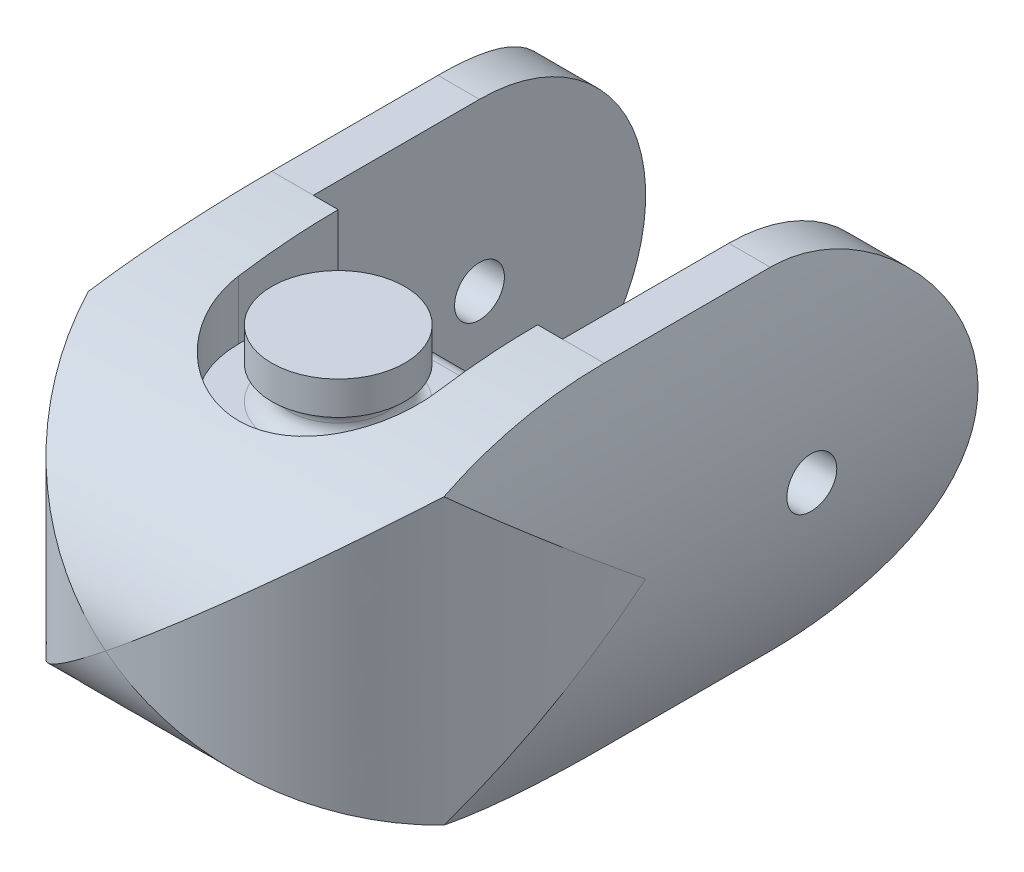
SolidWorks part; units mm, degrees
ref_plane "Alzado" through (0, 0, 0) normal (0, 0, 1) x (1, 0, 0)
ref_plane "Planta" through (0, 0, 0) normal (0, 1, 0) x (1, 0, 0)
ref_plane "Vista lateral" through (0, 0, 0) normal (1, 0, 0) x (0, 0, -1)
sketch "Croquis1" plane through (0, 0, 0) normal (0, 0, 1) x (1, 0, 0)
  line L1 (-10, 10) -> (10, 10)
  line L3 (-10, -10) -> (10, -10)
  line L5 (-10, 10) -> (10, -10) construction
  line L6 (-10, -10) -> (10, 10) construction
  arc A0 (-10, 10) -> (-10, -10) centre (8.75, 0) ccw
  arc A1 (10, -10) -> (10, 10) centre (-8.75, 0) ccw
  point P0 (0, 0)
  point P6 (-12.5, 0)
  point P8 (12.5, 0)
  dimension "D1" = 20
  dimension "D2" = 20
  dimension "D3" = 25
extrude "Saliente-Extruir1" add sketch "Croquis1" along normal blind 40
sketch "Croquis3" plane through (0, 0, 0) normal (0, 0, -1) x (-1, 0, 0)
  line L0 (10, -10) -> (-10, -10) construction
  circle A0 centre (0, -7) radius 1.5
  dimension "D2" = 3
  dimension "D1" = 3
extrude "Cortar-Extruir2" cut sketch "Croquis3" against normal blind 40
sketch "Croquis2" plane through (0, 0, 0) normal (0, 0, -1) x (-1, 0, 0)
  line L0 (10, -10) -> (-10, -10) construction
  line L5 (-7.5, 10) -> (7.5, 10)
  line L6 (-7.5, 10) -> (-7.5, -10)
  line L7 (-7.5, -10) -> (7.5, -10)
  line L8 (7.5, 10) -> (7.5, -10)
  line L9 (-7.5, 10) -> (7.5, -10) construction
  line L10 (-7.5, -10) -> (7.5, 10) construction
  point P0 (0, 0)
  dimension "D1" = 15
extrude "Cortar-Extruir1" cut sketch "Croquis2" against normal blind 20
sketch "Croquis4" plane through (0, 0, 0) normal (1, 0, 0) x (0, 0, -1)
  line L0 (0, -10) -> (0, 10) construction
  line L2 (-10, -10) -> (3, -10)
  line L4 (-10, 10) -> (3, 10)
  line L5 (3, -10) -> (3, 10)
  arc A0 (-10, -10) -> (-10, 10) centre (-10, 0) ccw
  circle A1 centre (-10, 0) radius 1.5
  dimension "D3" = 3
  dimension "D1" = 10
  dimension "D2" = 13
extrude "Cortar-Extruir3" cut sketch "Croquis4" against normal through all both and the other way through all
sketch "Croquis5" plane through (0, 0, 0) normal (0, 1, 0) x (1, 0, 0)
  line L0 (-7.5, -20) -> (7.5, -20) construction
  line L1 (-12.5, -11.5) -> (-12.5, -40) construction
  line L4 (-12.5, -20) -> (-12.5, -42)
  line L5 (-12.5, -42) -> (12.5, -42)
  line L6 (12.5, -20) -> (12.5, -42)
  ellipse E0 centre (0, -20) end of major axis (0, -40) minor radius 12.5 (-12.5, -20) -> (12.5, -20) ccw
  dimension "D1" = 22
extrude "Cortar-Extruir4" cut sketch "Croquis5" against normal through all both and the other way through all
sketch "Croquis6" plane through (0, 0, 0) normal (1, 0, 0) x (0, 0, -1)
  line L1 (-20, 10) -> (-42, 10)
  line L3 (-20, -10) -> (-42, -10)
  line L4 (-42, 10) -> (-42, -10)
  ellipse E0 centre (-20, 0) end of major axis (-40, 0) minor radius 10 (-20, 10) -> (-20, -10) ccw
  dimension "D1" = 22
extrude "Cortar-Extruir5" cut sketch "Croquis6" against normal through all both and the other way through all
ref_plane "Plane1" through (0, 10, 0) normal (0, 1, 0) x (1, 0, 0)
sketch "Sketch1" plane through (0, 10, 0) normal (0, 1, 0) x (1, 0, 0)
  line L0 (-7.5, -20) -> (7.5, -20) construction
  line L3 (-6, -26) -> (-6, -20)
  line L4 (-6, -20) -> (6, -20)
  line L5 (6, -26) -> (6, -20)
  arc A0 (-6, -26) -> (6, -26) centre (0, -26) ccw
  dimension "D1" = 12
  dimension "D2" = 6
extrude "Cut-Extrude1" cut sketch "Sketch1" against normal blind 4
sketch "Sketch2" plane through (0, 6, 0) normal (0, 1, 0) x (1, 0, 0)
  circle A0 centre (0, -26) radius 3
  dimension "D1" = 6
extrude "Boss-Extrude1" add sketch "Sketch2" along normal blind 2
sketch "Sketch3" plane through (0, 8, 0) normal (0, 1, 0) x (1, 0, 0)
  circle A0 centre (0, -26) radius 4
  dimension "D1" = 8
extrude "Boss-Extrude2" add sketch "Sketch3" along normal blind 2
fillet "Fillet1" radius 1 2 edges at (0, 8, 29) (0, 6, 29)
fillet "Fillet2" radius 1 1 edges at (0, 6, 20)
fillet "Fillet3" radius 1 1 edges at (-1.5, -7, 20)
